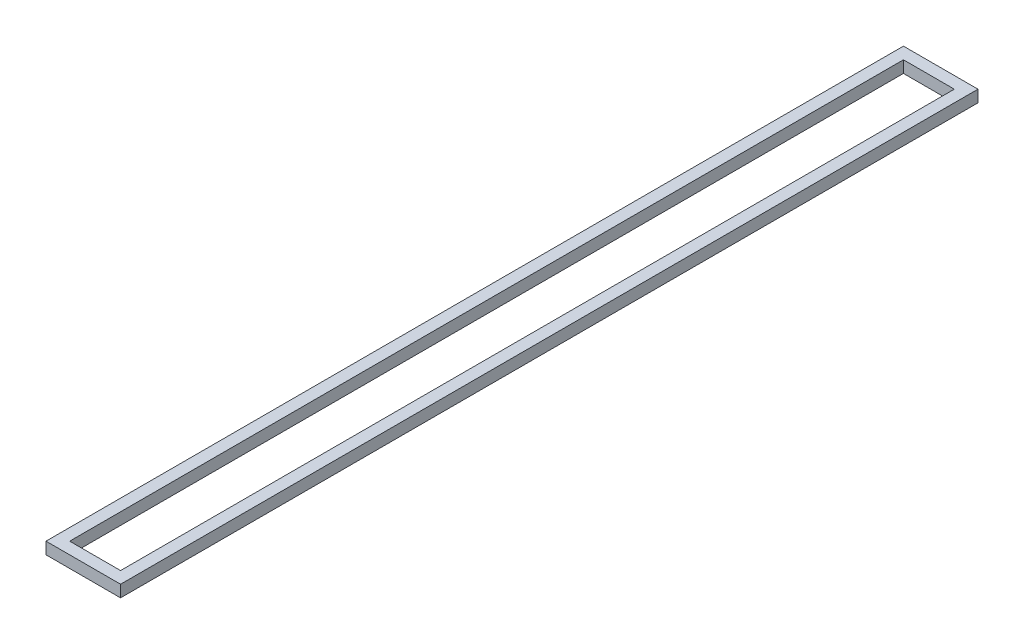
SolidWorks part; units mm, degrees
ref_plane "Front Plane" through (0, 0, 0) normal (0, 0, 1) x (1, 0, 0)
ref_plane "Top Plane" through (0, 0, 0) normal (0, 1, 0) x (1, 0, 0)
ref_plane "Right Plane" through (0, 0, 0) normal (1, 0, 0) x (0, 0, -1)
sketch "Sketch1" plane through (0, 0, 0) normal (0, 1, 0) x (1, 0, 0)
  line L1 (-50, 575) -> (50, 575)
  line L2 (-50, 575) -> (-50, -575)
  line L3 (-50, -575) -> (50, -575)
  line L4 (50, 575) -> (50, -575)
  line L8 (-34.125, 559.125) -> (34.125, 559.125)
  line L9 (34.125, 559.125) -> (34.125, -559.125)
  line L10 (-34.125, -559.125) -> (34.125, -559.125)
  line L11 (-34.125, 559.125) -> (-34.125, -559.125)
  point P4 (0, 575)
  point P6 (50, 0)
  dimension "D1" = 100
  dimension "D2" = 1150
  dimension "D3" = 15.875
extrude "Boss-Extrude1" add sketch "Sketch1" along normal blind 15.875
